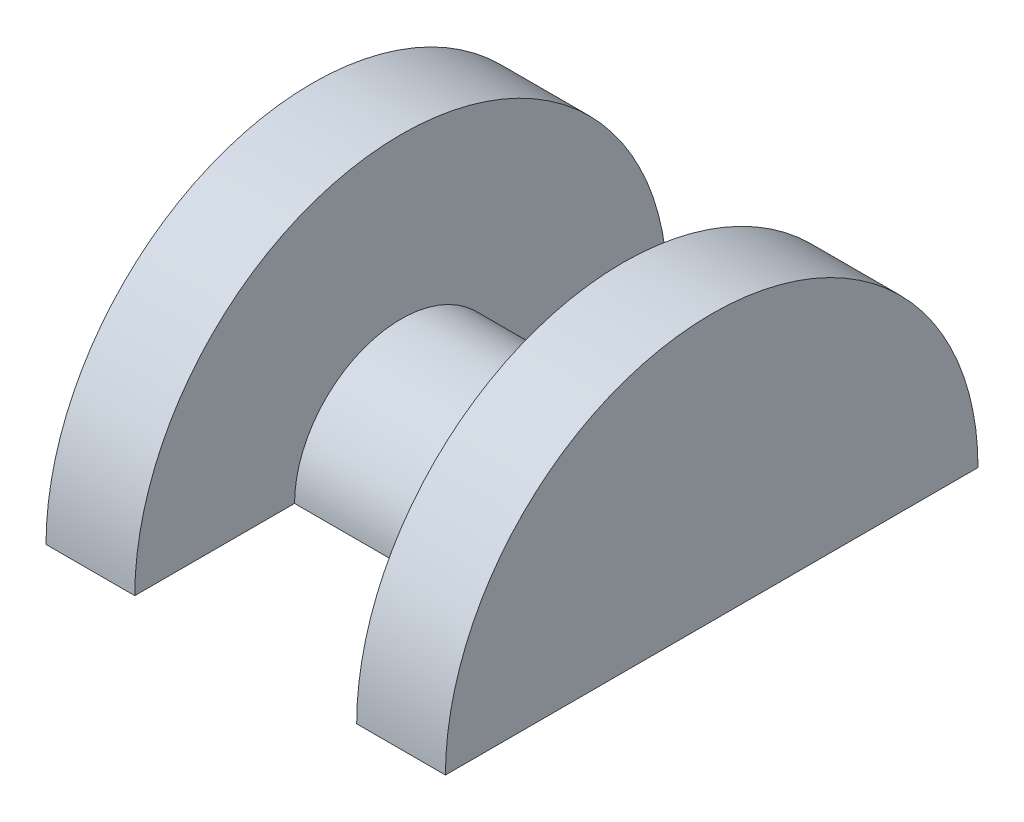
SolidWorks part; units mm, degrees
ref_plane "Front Plane" through (0, 0, 0) normal (0, 0, 1) x (1, 0, 0)
ref_plane "Top Plane" through (0, 0, 0) normal (0, 1, 0) x (1, 0, 0)
ref_plane "Right Plane" through (0, 0, 0) normal (1, 0, 0) x (0, 0, -1)
sketch "Sketch1" plane through (0, 0, 0) normal (1, 0, 0) x (0, 0, -1)
  line L0 (-3, 0) -> (3, 0)
  arc A0 (3, 0) -> (-3, 0) centre (0, 0) ccw
  arc A1 (1.2, 0) -> (-1.2, 0) centre (0, 0) ccw
  dimension "D1" = 6
  dimension "D2" = 2.4
extrude "Boss-Extrude1" add sketch "Sketch1" along normal blind 1 contours A1 L0 A0 | L0 A1 region at (0, 1.4188, 0) region at (0, 0.5093, 0)
extrude "Boss-Extrude2" add sketch "Sketch1<3>" against normal blind 1.25 contours L0 A1 region at (0, 0.5093, 0)
sketch "Sketch1<3>" plane through (0, 0, 0) normal (1, 0, 0) x (0, 0, -1) same geometry as "Sketch1"
ref_plane "Plane1" through (-1.25, 0, 0) normal (-1, 0, 0) x (0, 0, 1)
mirror "Mirror1" about plane through (-1.25, 0, 0) normal (-1, 0, 0) of bodies 102
